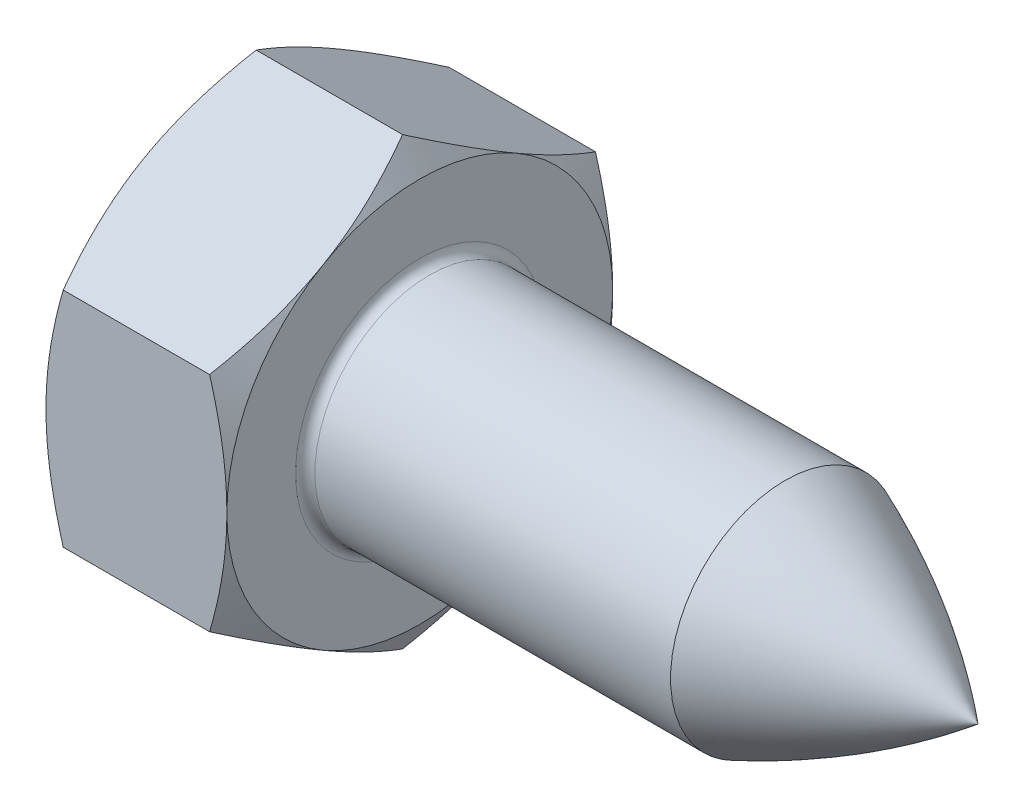
SolidWorks part; units mm, degrees
ref_plane "Front" through (0, 0, 0) normal (0, 0, 1) x (1, 0, 0)
ref_plane "Top" through (0, 0, 0) normal (0, 1, 0) x (1, 0, 0)
ref_plane "Right" through (0, 0, 0) normal (1, 0, 0) x (0, 0, -1)
sketch "Sketch2" plane through (0, 0, 0) normal (1, 0, 0) x (0, 0, -1)
  line L1 (0, 9.2376) -> (-8, 4.6188)
  line L2 (-8, 4.6188) -> (-8, -4.6188)
  line L3 (-8, -4.6188) -> (0, -9.2376)
  line L4 (0, -9.2376) -> (8, -4.6188)
  line L5 (8, -4.6188) -> (8, 4.6188)
  line L6 (8, 4.6188) -> (0, 9.2376)
  circle A0 centre (0, 0) radius 8 construction
extrude "BaseHead" add sketch "Sketch2" along normal blind 7.5
sketch "Sketch1" plane through (0, 0, 0) normal (0, 0, 1) x (1, 0, 0)
  line L0 (-9.5445, 0) -> (41.9665, 0) construction
  line L1 (30.65, 0) -> (30.65, 4.75)
  line L2 (30.65, 4.75) -> (7.5, 4.75)
  line L3 (7.5, 4.75) -> (7.5, 0)
  line L4 (30.65, 0) -> (7.5, 0)
  line L5 (7.5, 4.6188) -> (7.5, -4.6188) construction
  line L6 (9.6, 7.9549) -> (9.6, -2.6884) construction
  dimension "l" = 23.15
revolve "BaseBody" add sketch "Sketch1" angle 360 about L0
cosmetic thread "ThreadCosmetic1" [suppressed] parameters "D1"=21.05, "D2"=8.5
sketch "Sketch3" plane through (0, 0, 0) normal (0, 0, 1) x (1, 0, 0)
  line L0 (10.6638, 0) -> (-1.5125, 0) construction
  line L2 (0, 8) -> (0.7145, 9.2376)
  line L5 (0.7145, 9.2376) -> (0, 9.2376)
  line L6 (0, 9.2376) -> (0, 8)
  line L7 (3.75, 9.2376) -> (3.75, 3.7337) construction
  line L8 (7.5, 9.2376) -> (7.5, 8)
  line L9 (6.7855, 9.2376) -> (7.5, 9.2376)
  line L10 (7.5, 8) -> (6.7855, 9.2376)
  dimension "D1" = 16
  dimension "D2" = 30
revolve "Cut-Revolve7" cut sketch "Sketch3" angle 360 about L0
fillet "Fillet1" radius 0.4 1 edges at (7.5, 0, 4.75)
sketch "Sketch4" plane through (0, 0, 0) normal (0, 0, 1) x (1, 0, 0)
  line L0 (31.9782, 0) -> (17.0112, 0) construction
  line L2 (26.45, -4.75) -> (28.55, -4.75)
  line L3 (28.55, -4.75) -> (30.65, -4.225)
  line L5 (30.65, -4.75) -> (30.65, 4.75) construction
  line L6 (26.45, -4.75) -> (26.45, -5.25)
  line L7 (26.45, -5.25) -> (30.65, -5.25)
  line L8 (30.65, -5.25) -> (30.65, -4.225)
  point P15 (28.55, -4.75)
  dimension "D2" = 2.1
  dimension "D4" = 0.5
  dimension "D1" = 9.5
  dimension "D3" = 0.525
revolve "Cut-Revolve1" cut sketch "Sketch4" angle 360 about L0
sketch "Sketch5" plane through (0, 0, 0) normal (0, 0, 1) x (1, 0, 0)
  line L0 (33.3907, 0) -> (10.0621, 0) construction
  line L2 (30.65, -4.75) -> (30.65, 4.75) construction
  line L3 (30.65, 0) -> (22.65, -4.75) construction
  line L6 (30.65, 0) -> (31.15, 0)
  line L7 (22.65, -4.75) -> (30.65, -4.75)
  line L8 (31.15, 0) -> (31.15, -4.75)
  line L9 (31.15, -4.75) -> (30.65, -4.75)
  arc A0 (30.65, 0) -> (22.65, -4.75) centre (10.4863, 24.8481) cw
  dimension "D1" = 32
  dimension "D3" = 9.5
  dimension "D2" = 0.5
revolve "Cut-Revolve6" cut sketch "Sketch5" angle 360 about L0
sketch "Sketch6" plane through (0, 0, 0) normal (0, 0, 1) x (1, 0, 0)
  line L0 (0, 0) -> (-3.8452, 0) construction
  line L1 (-0.1, 6.6667) -> (1.25, 6.6667)
  line L2 (-0.1, 6.6667) -> (-0.1, 0)
  line L3 (-0.1, 0) -> (1.25, 0)
  line L4 (1.25, 6.6667) -> (1.25, 0)
  dimension "D1" = 0.1
  dimension "D2" = 1.25
  dimension "D3" = 13.3333
revolve "Cut-Revolve8" cut sketch "Sketch6" angle 360 about L0
sketch "Sketch7" plane through (0, 0, 0) normal (0, 0, 1) x (1, 0, 0)
  line L0 (9.35, 5.25) -> (9.85, 5.25)
  line L1 (9.85, 5.25) -> (9.85, 4.75)
  line L2 (9.85, 4.75) -> (9.6, 4.317)
  line L3 (9.6, 4.317) -> (9.35, 4.75)
  line L4 (9.35, 4.75) -> (9.35, 5.25)
  line L5 (0, 0) -> (7.2002, 0) construction
  line L6 (7.5, 0) -> (7.5, 6.9282) construction
  dimension "D2" = 2.1
  dimension "D1" = 9.5
  dimension "D3" = 0.5
revolve "Cut-Revolve10" [suppressed] cut sketch "Sketch7" angle 360 about L5
pattern_linear "LPattern10" [suppressed] count 35 spacing 0.6 along (1, 0, 0) of bodies 107
equation "\"D3@Sketch4\" = \"yf@Sketch4\" / 8"
equation "\"D2@ThreadCosmetic1\" = \"st@Sketch1\" - 1"
equation "\"D1@Sketch5\" = \"yc@Sketch5\" * 4"
equation "\"D3@Sketch5\" = \"st@Sketch1\""
equation "\"D2@Sketch4\" = \"yf@Sketch4\" / 2"
equation "\"D1@Sketch3\" = \"s@Sketch2\""
equation "\"D1@Sketch4\" = \"st@Sketch1\""
equation "\"D1@ThreadCosmetic1\" = \"l@Sketch1\" - \"a@Sketch1\""
equation "\"D2@Sketch6\" = \"k@BaseHead\"  / 6"
equation "\"D3@Sketch6\" = \"s@Sketch2\" * 5 / 6"
equation "\"D1@Sketch7\" = \"st@Sketch1\""
equation "\"D2@Sketch7\" = \"a@Sketch1\""
equation "\"D3@Sketch7\" = (  \"D1@Sketch7\" - \"D2@ThreadCosmetic1\" )  / 2"
equation "\"D3@LPattern10\" = \"D3@Sketch7\" * 1.2"
equation "\"D1@LPattern10\" = \"D1@ThreadCosmetic1\" / \"D3@LPattern10\""
